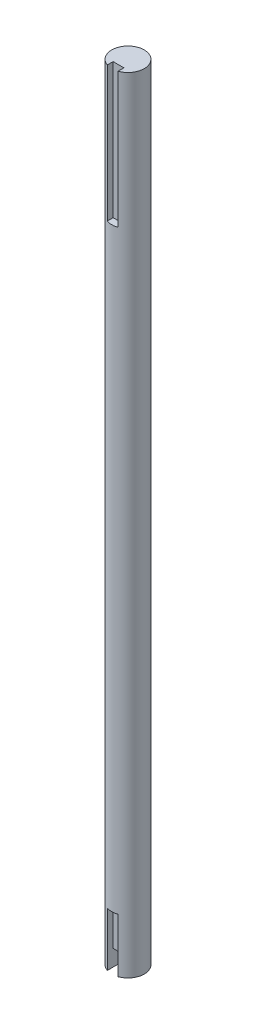
SolidWorks part; units mm, degrees
ref_plane "Front Plane" through (0, 0, 0) normal (0, 0, 1) x (1, 0, 0)
ref_plane "Top Plane" through (0, 0, 0) normal (0, 1, 0) x (1, 0, 0)
ref_plane "Right Plane" through (0, 0, 0) normal (1, 0, 0) x (0, 0, -1)
sketch "Sketch1" plane through (0, 0, 0) normal (0, 1, 0) x (1, 0, 0)
  circle A0 centre (0, 0) radius 6
  point P4 (0, 0)
  dimension "D1" = 12
extrude "Boss-Extrude1" add sketch "Sketch1" along normal blind 254 and the other way blind 36
sketch "Sketch2" plane through (0, 0, 0) normal (0, 1, 0) x (1, 0, 0)
  line L1 (-2, -8.5) -> (2, -8.5)
  line L2 (-2, -8.5) -> (-2, -3.5)
  line L3 (-2, -3.5) -> (2, -3.5)
  line L4 (2, -8.5) -> (2, -3.5)
  line L5 (-2, -8.5) -> (2, -3.5) construction
  line L6 (-2, -3.5) -> (2, -8.5) construction
  circle A0 centre (0, 0) radius 6 construction
  point P0 (0, -6)
  dimension "D1" = 2.5
  dimension "D2" = 4
extrude "Cut-Extrude3" cut sketch "Sketch2" against normal blind 0.0001 and the other way blind 20 from surface starting at face at (0, -36, 6)
extrude "Cut-Extrude4" cut sketch "Sketch2<2>" against normal blind 50 from surface starting at face at (0, 254, 6)
sketch "Sketch2<2>" plane through (0, 0, 0) normal (0, 1, 0) x (1, 0, 0) same geometry as "Sketch2"
sketch "Sketch3" plane through (0, 0, 0) normal (0, 1, 0) x (1, 0, 0)
  line L1 (-2, -11) -> (2, -11)
  line L2 (-2, -11) -> (-2, -1)
  line L3 (-2, -1) -> (2, -1)
  line L4 (2, -11) -> (2, -1)
  line L5 (-2, -11) -> (2, -1) construction
  line L6 (-2, -1) -> (2, -11) construction
  arc A0 (-2, -5.6569) -> (2, -5.6569) centre (0, 0) ccw construction
  point P0 (0, -6)
  dimension "D1" = 4
  dimension "D2" = 5
extrude "Cut-Extrude6" cut sketch "Sketch3" along normal blind 6 from surface starting at face at (0, -36, 1.6642)
